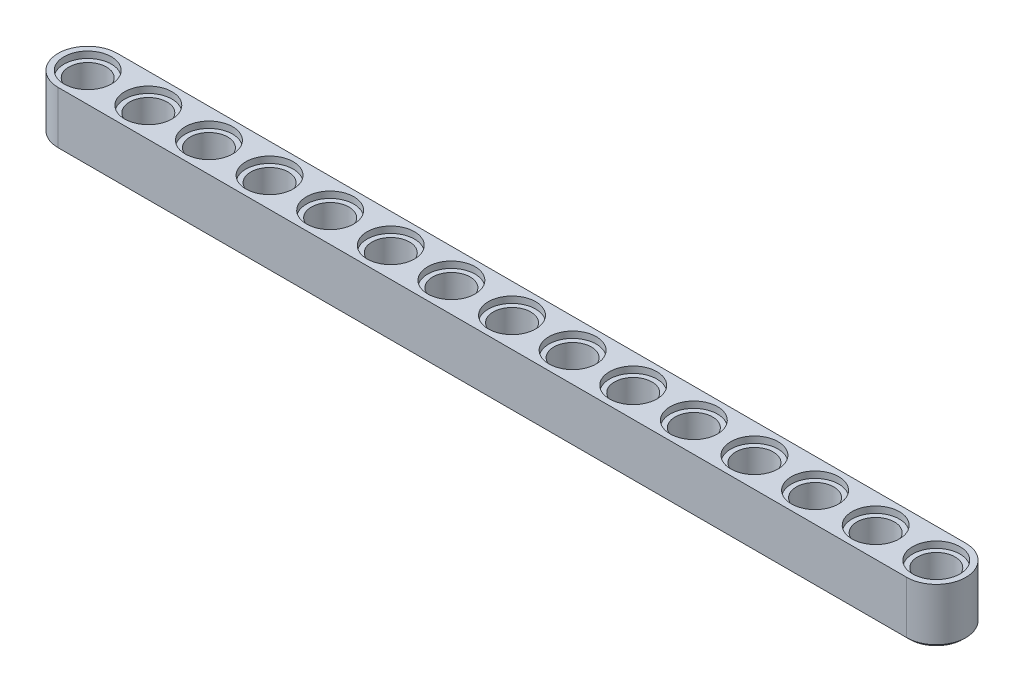
SolidWorks part; units mm, degrees
ref_plane "Front Plane" through (0, 0, 0) normal (0, 0, 1) x (1, 0, 0)
ref_plane "Top Plane" through (0, 0, 0) normal (0, 1, 0) x (1, 0, 0)
ref_plane "Right Plane" through (0, 0, 0) normal (1, 0, 0) x (0, 0, -1)
sketch "Sketch1" plane through (0, 0, 0) normal (0, 1, 0) x (1, 0, 0)
  line L0 (0, 0) -> (112, 0) construction
  line L1 (0, 3.9) -> (112, 3.9)
  line L2 (0, -3.9) -> (112, -3.9)
  arc A0 (0, 3.9) -> (0, -3.9) centre (0, 0) ccw
  arc A1 (112, -3.9) -> (112, 3.9) centre (112, 0) ccw
  point P3 (56, 0)
  dimension "D1" = 112
  dimension "D2" = 7.8
extrude "Boss-Extrude1" add sketch "Sketch1" along normal blind 7.3
sketch "Sketch2" plane through (0, 7.3, 0) normal (0, 1, 0) x (1, 0, 0)
  circle A0 centre (0, 0) radius 2.475
  dimension "D1" = 4.95
extrude "Cut-Extrude1" cut sketch "Sketch2" against normal through all
sketch "Sketch3" plane through (0, 7.3, 0) normal (0, 1, 0) x (1, 0, 0)
  circle A0 centre (0, 0) radius 3.125
  dimension "D1" = 6.25
extrude "Cut-Extrude2" cut sketch "Sketch3" against normal blind 0.85
ref_plane "Plane1" through (0, 3.65, 0) normal (0, 1, 0) x (1, 0, 0)
mirror "Mirror1" about plane through (0, 3.65, 0) normal (0, 1, 0) of "Cut-Extrude2"
pattern_linear "LPattern1" count 15 spacing 8 along (1, 0, 0) of "Cut-Extrude1", "Cut-Extrude2", "Mirror1"
chamfer "Chamfer1" distance 0.4 angle 45 19 edges at (56, 0, 3.9) (115.9, 0, 0) (56, 0, -3.9) (-3.9, 0, 0) (0, 0, 3.125) (8, 0, 3.125) (16, 0, 3.125) (24, 0, 3.125) (32, 0, 3.125) (40, 0, 3.125) (48, 0, 3.125) (56, 0, 3.125) (64, 0, 3.125) (72, 0, 3.125) (80, 0, 3.125) (88, 0, 3.125) (96, 0, 3.125) (104, 0, 3.125) (112, 0, 3.125)
equation "\"Pitch\"= 8"
equation "\"Beam_Height\"= 7.8"
equation "\"Beam_Width\"= 7.3"
equation "\"Pin_Hole_Dia\"= 4.95"
equation "\"CBore_Dia\"= 6.25"
equation "\"CBore_Depth\"= 0.85"
equation "\"D2@Sketch1\"=\"Beam_Height\""
equation "\"D1@Boss-Extrude1\"=\"Beam_Width\""
equation "\"D1@Sketch2\"=\"Pin_Hole_Dia\""
equation "\"D1@Sketch3\"=\"CBore_Dia\""
equation "\"D1@Cut-Extrude2\"=\"CBore_Depth\""
equation "\"D3@LPattern1\"=\"Pitch\""
